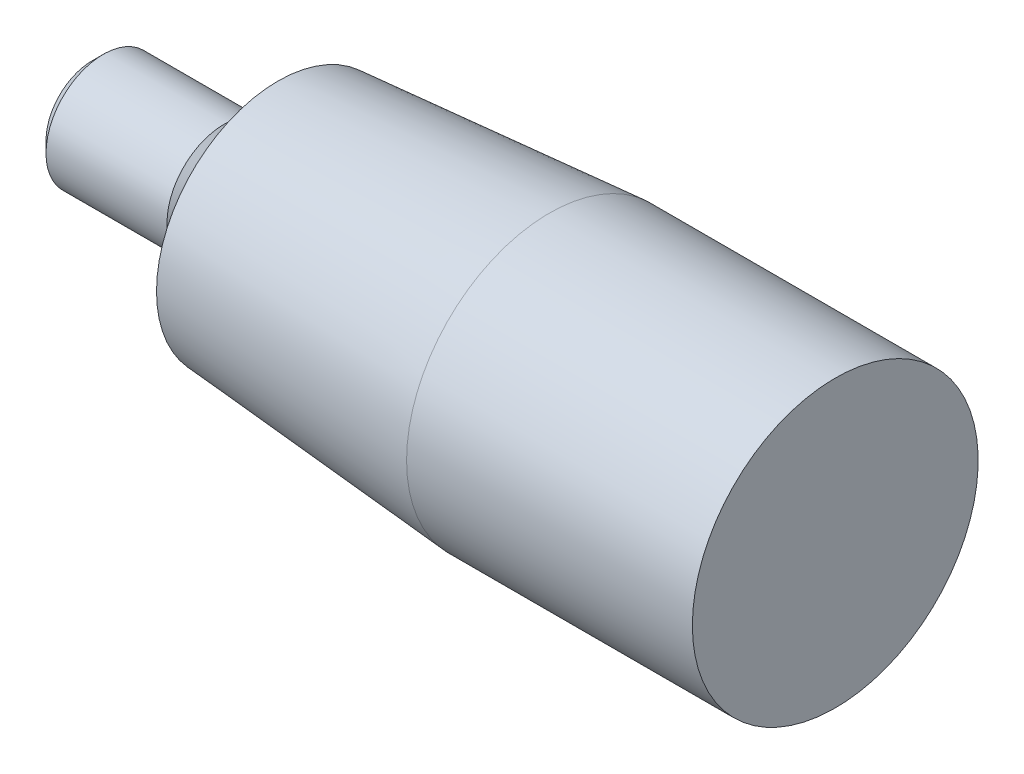
SolidWorks part; units mm, degrees
ref_plane "前视基准面" through (0, 0, 0) normal (0, 0, 1) x (1, 0, 0)
ref_plane "上视基准面" through (0, 0, 0) normal (0, 1, 0) x (1, 0, 0)
ref_plane "右视基准面" through (0, 0, 0) normal (1, 0, 0) x (0, 0, -1)
ref_plane "基准面4" through (0, 0, 0) normal (0, 0, 1) x (1, 0, 0)
sketch "草图1" plane through (0, 0, 0) normal (0, 0, 1) x (1, 0, 0)
  line L0 (-13, 0) -> (-13, 3.233)
  line L1 (-13, 3.233) -> (-12.233, 4)
  line L2 (-12.233, 4) -> (-3.767, 4)
  line L3 (-3.767, 4) -> (-3.0905, 3.3235)
  line L4 (-3.0905, 3.3235) -> (-1, 3.3235)
  line L5 (-1, 3.3235) -> (-1, 5)
  line L6 (-1, 5) -> (0, 5)
  line L7 (0, 5) -> (0, 8.5)
  line L8 (0, 8.5) -> (19, 10)
  line L9 (19, 10) -> (39, 10)
  line L10 (39, 10) -> (39, 0)
  line L11 (39, 0) -> (-13, 0)
  line L12 (39, 0) -> (0, 0) construction
revolve "旋转1" add sketch "草图1" angle 360 about L12 reverse direction yes
cosmetic thread "装饰螺纹线1" parameters "D1"=2.0905, "D2"=6.466
ref_plane "基准面5" through (-13, 0, 0) normal (1, 0, 0) x (0, 0, -1)
sketch "草图2" plane through (-13, 0, 0) normal (1, 0, 0) x (0, 0, -1)
  line L0 (-2, 1.1547) -> (-2, -1.1547)
  line L1 (-2, -1.1547) -> (0, -2.3094)
  line L2 (0, -2.3094) -> (2, -1.1547)
  line L3 (2, -1.1547) -> (2, 1.1547)
  line L4 (2, 1.1547) -> (0, 2.3094)
  line L5 (0, 2.3094) -> (-2, 1.1547)
extrude "切除-拉伸1" cut sketch "草图2" along normal blind 4
sketch "草图3" plane through (0, 0, 0) normal (0, 0, 1) x (1, 0, 0)
  line L0 (-9, 0) -> (-9, 2.3094)
  line L1 (-9, 2.3094) -> (-7.67, 0)
  line L2 (-7.67, 0) -> (-9, 0)
  line L3 (-7.67, 0) -> (-9, 0) construction
revolve "切除-旋转1" cut sketch "草图3" angle 360 about L3 reverse direction yes
ref_plane "基准面6" through (-1, 0, 0) normal (1, 0, 0) x (0, 0, -1)
ref_plane "to_handle XY" through (-1, 0, 0) normal (-1, 0, 0) x (0, 0, 1)
ref_plane "to_handle XZ" through (0, 0, 0) normal (0, 1, 0) x (1, 0, 0)
ref_plane "to_handle YZ" through (0, 0, 0) normal (0, 0, -1) x (-1, 0, 0)
ref_axis "to_handle X" through (-1, 0, 80.9) along (0, 0, -1)
ref_axis "to_handle Y" through (-1, 50, 0) along (0, -1, 0)
ref_axis "to_handle Z" through (-80.9, 0, 0) along (1, 0, 0)
sketch3d "to_handle"
  point P0 (-1, 0, 0)
